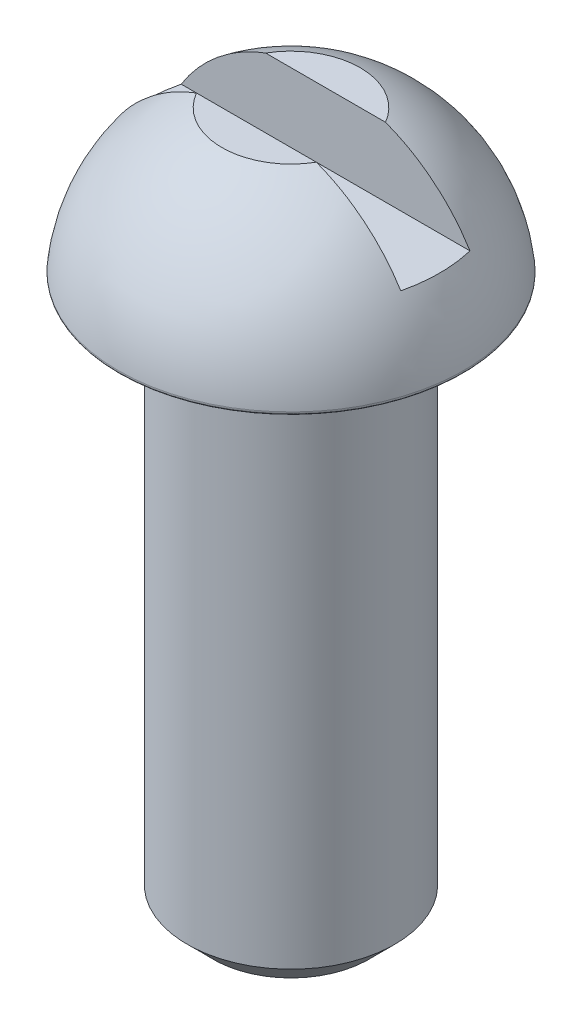
SolidWorks part; units mm, degrees
ref_plane "Спереди" through (0, 0, 0) normal (0, 0, 1) x (1, 0, 0)
ref_plane "Сверху" through (0, 0, 0) normal (0, 1, 0) x (1, 0, 0)
ref_plane "Справа" through (0, 0, 0) normal (1, 0, 0) x (0, 0, -1)
sketch "Эскиз1" plane through (0, 0, 0) normal (0, 0, 1) x (1, 0, 0)
  line L0 (5, 16) -> (3, 16)
  line L1 (0, 0) -> (0, 20.2)
  line L2 (3, 16) -> (3, 0.75)
  line L3 (3, 0.75) -> (2.25, 0)
  line L4 (2.25, 0) -> (0, 0)
  line L5 (0, 20.2) -> (2, 20.2)
  arc A0 (2, 20.2) -> (5, 16) centre (0.0152, 15.6108) cw
  point P9 (0, 0)
  dimension "D2" = 2
  dimension "D3" = 5
  dimension "D1" = 16
  dimension "D4" = 2.25
  dimension "D5" = 4.2
  dimension "D6" = 5
  dimension "D7" = 45
  dimension "D9" = 3
revolve "Повернуть1" add sketch "Эскиз1" angle 360 about L1
fillet "Скругление1" radius 0.1 1 edges at (0, 16, -5)
sketch "Эскиз3" plane through (0, 20.2, 0) normal (0, 1, 0) x (-1, 0, 0)
  line L1 (5, -1) -> (-5, -1)
  line L2 (5, -1) -> (5, 1)
  line L3 (5, 1) -> (-5, 1)
  line L4 (-5, -1) -> (-5, 1)
  dimension "D1" = 2
  dimension "D2" = 1
  dimension "D3" = 10
  dimension "D4" = 5
extrude "Вырез-Вытянуть2" cut sketch "Эскиз3" against normal blind 2
ref_axis "Ось1" through (0, -104.1565, 0) along (0, 1, 0)
